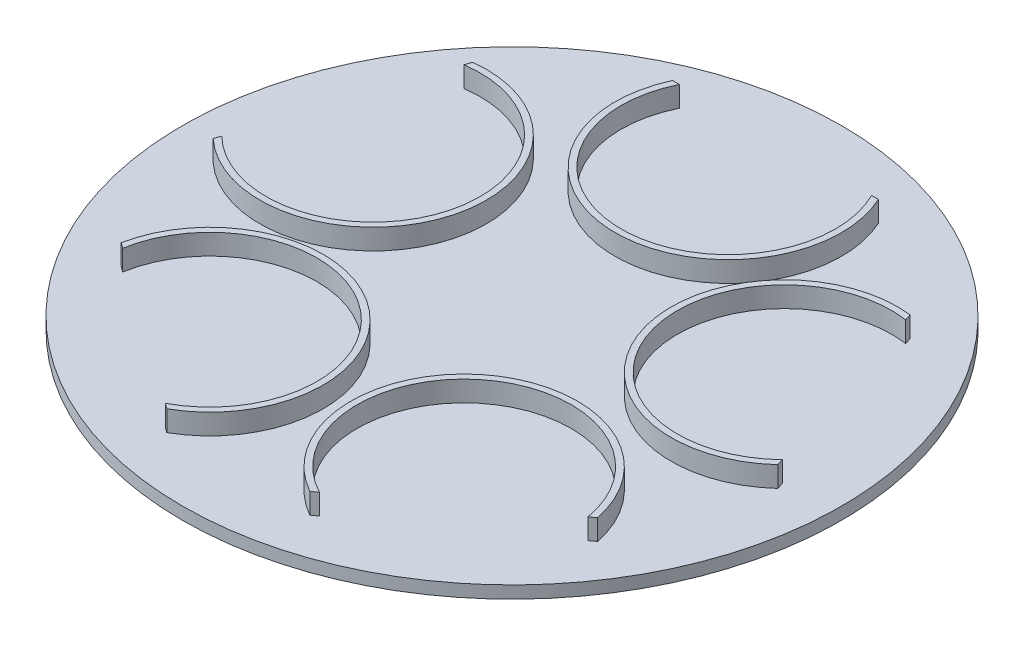
SolidWorks part; units mm, degrees
ref_plane "前视基准面" through (0, 0, 0) normal (0, 0, 1) x (1, 0, 0)
ref_plane "上视基准面" through (0, 0, 0) normal (0, 1, 0) x (1, 0, 0)
ref_plane "右视基准面" through (0, 0, 0) normal (1, 0, 0) x (0, 0, -1)
sketch "草图1" plane through (0, 0, 0) normal (0, 1, 0) x (1, 0, 0)
  line L0 (0, -1000) -> (0, 49000) construction
  line L1 (-25, 63.9564) -> (-23.3399, 63.9564)
  line L2 (23.3399, 63.9564) -> (25, 63.9564)
  line L3 (68.0386, -2.4339) -> (68.5516, -4.0128)
  line L4 (53.1008, 43.54) -> (53.6138, 41.9612)
  line L5 (18.7103, -65.4607) -> (17.3672, -66.4365)
  line L6 (57.8181, -37.0472) -> (56.475, -38.023)
  line L7 (-56.475, -38.023) -> (-57.8181, -37.0472)
  line L8 (-17.3672, -66.4365) -> (-18.7103, -65.4607)
  line L9 (-53.6138, 41.9612) -> (-53.1008, 43.54)
  line L10 (-68.5516, -4.0128) -> (-68.0386, -2.4339)
  circle A0 centre (0, 0) radius 80
  arc A1 (-25, 63.9564) -> (25, 63.9564) centre (0, 52.5) ccw
  arc A2 (-23.3399, 63.9564) -> (23.3399, 63.9564) centre (0, 52.5) ccw
  arc A3 (53.1008, 43.54) -> (68.5516, -4.0128) centre (49.9305, 16.2234) ccw
  arc A4 (53.6138, 41.9612) -> (68.0386, -2.4339) centre (49.9305, 16.2234) ccw
  circle A5 centre (0, 0) radius 80
  arc A6 (57.8181, -37.0472) -> (17.3672, -66.4365) centre (30.8587, -42.4734) ccw
  arc A7 (56.475, -38.023) -> (18.7103, -65.4607) centre (30.8587, -42.4734) ccw
  circle A8 centre (0, 0) radius 80
  arc A9 (-17.3672, -66.4365) -> (-57.8181, -37.0472) centre (-30.8587, -42.4734) ccw
  arc A10 (-18.7103, -65.4607) -> (-56.475, -38.023) centre (-30.8587, -42.4734) ccw
  circle A11 centre (0, 0) radius 80
  arc A12 (-68.5516, -4.0128) -> (-53.1008, 43.54) centre (-49.9305, 16.2234) ccw
  arc A13 (-68.0386, -2.4339) -> (-53.6138, 41.9612) centre (-49.9305, 16.2234) ccw
  circle A14 centre (0, 0) radius 80
  point P37 (0, 0)
  dimension "D1" = 160
  dimension "D2" = 55
  dimension "D3" = 52
  dimension "D4" = 50
  dimension "D5" = 5
extrude "凸台-拉伸1" add sketch "草图1" along normal blind 3 contours L0 A0 A2 L2 A1 L4 A4 L3 A3 L6 A7 L5 A6 | A14 L0 A1 L1 A2 L10 A13 L9 A12 L8 A10 L7 A9 region at (-34.1721, 0, 0) region at (34.1721, 0, 0)
extrude "凸台-拉伸2" add sketch "草图1<5>" along normal blind 8 contours A9 L7 A10 L8 | A12 L9 A13 L10 | A1 L2 A2 L1 | A4 L3 A3 L4 | A6 L5 A7 L6
sketch "草图1<5>" plane through (0, 0, 0) normal (0, 1, 0) x (1, 0, 0) same geometry as "草图1"
